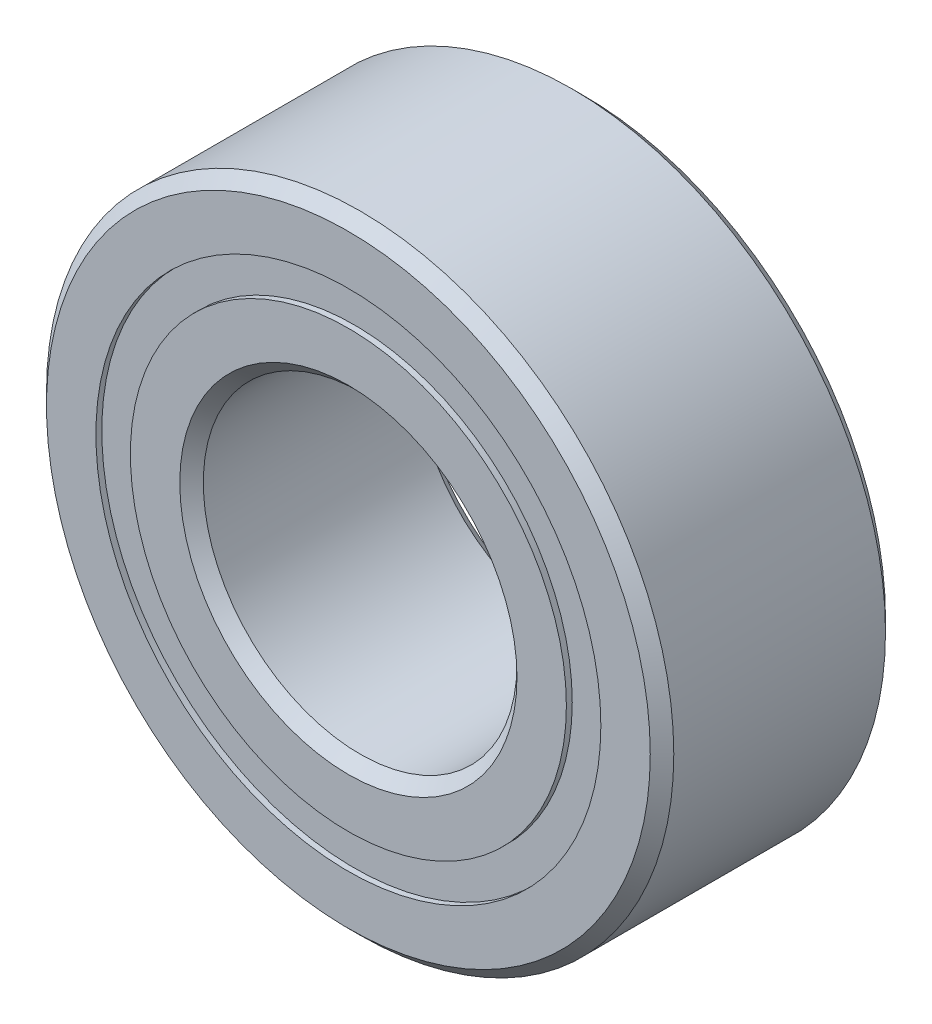
SolidWorks part; units mm, degrees
material "Ceramic Porcelain"
ref_plane "Front Plane" through (0, 0, 0) normal (0, 0, 1) x (1, 0, 0)
ref_plane "Top Plane" through (0, 0, 0) normal (0, 1, 0) x (1, 0, 0)
ref_plane "Right Plane" through (0, 0, 0) normal (1, 0, 0) x (0, 0, -1)
sketch "Sketch1" plane through (0, 0, 0) normal (1, 0, 0) x (0, 0, -1)
  line L0 (-3, 0) -> (3, 0) construction
  line L1 (0, 8) -> (0, -8) construction
  line L2 (2.7, 8) -> (-2.7, 8)
  line L3 (-2.7, 8) -> (-3, 7.7)
  line L4 (-3, 7.7) -> (-3, 6.4396)
  line L5 (-3, 6.4396) -> (-1.3333, 6.4396)
  line L6 (3, 6.4396) -> (1.3333, 6.4396)
  line L7 (3, 7.7) -> (3, 6.4396)
  line L8 (2.7, 8) -> (3, 7.7)
  line L9 (0, 8) -> (0, 6) construction
  line L10 (0, 6) -> (0, 4) construction
  arc A0 (-1.3333, 6.4396) -> (1.3333, 6.4396) centre (0, 6) cw
  point P14 (0, 4)
  dimension "D3" = 2.6667
  dimension "D1" = 45
  dimension "Width" = 6
  dimension "OD" = 16
  dimension "D2" = 0.3
  dimension "Shaft Dia" = 8
  dimension "D4" = 0.4396
revolve "Revolve1" add sketch "Sketch1" angle 360 about L0
sketch "Sketch3" plane through (0, 0, 0) normal (1, 0, 0) x (0, 0, -1)
  line L0 (-3, 5.5604) -> (-1.3333, 5.5604)
  line L1 (0, 8) -> (0, -8) construction
  line L2 (-3, 7.7) -> (-3, 6.4396) construction
  line L3 (-3, 5.5604) -> (-3, 4.3)
  line L4 (-2.7, 8) -> (-3, 7.7) construction
  line L5 (-3, 4.3) -> (-2.7, 4)
  line L6 (-2.7, 4) -> (2.7, 4)
  line L7 (2.7, 8) -> (2.7, -8) construction
  line L8 (2.7, 4) -> (3, 4.3)
  line L9 (3, -7.7) -> (3, 7.7) construction
  line L10 (3, 4.3) -> (3, 5.5604)
  line L11 (3, 5.5604) -> (1.3333, 5.5604)
  line L13 (2.7, 8) -> (3, 7.7) construction
  arc A0 (1.3333, 6.4396) -> (-1.3333, 6.4396) centre (0, 6) ccw construction
  arc A1 (1.3333, 5.5604) -> (-1.3333, 5.5604) centre (0, 6) cw
revolve "Revolve3" add sketch "Sketch3" angle 360 about L0
sketch "Sketch4" plane through (0, 0, 0) normal (1, 0, 0) x (0, 0, -1)
  line L0 (-1.4039, 6) -> (1.4039, 6)
  arc A2 (-1.4039, 6) -> (1.4039, 6) centre (0, 6) cw
  arc A3 (1.3333, 6.4396) -> (-1.3333, 6.4396) centre (0, 6) ccw construction
revolve "Revolve4" add sketch "Sketch4" angle 360 about L0
ref_axis "Axis1" through (0, 0, -3) along (0, 0, 1)
pattern_circular "CirPattern1" count 12 every 30 about axis through (0, 0, -3) along (0, 0, 1) of bodies 104
sketch "Sketch5" plane through (0, 0, 0) normal (1, 0, 0) x (0, 0, -1)
  line L0 (-3, 6.4396) -> (-1.3333, 6.4396) construction
  line L1 (-2.85, 6.4396) -> (-1.4039, 6.4396)
  line L2 (-2.85, 6.4396) -> (-2.85, 5.5604)
  line L3 (-2.85, 5.5604) -> (-1.4039, 5.5604)
  line L4 (-1.4039, 6.4396) -> (-1.4039, 5.5604)
  line L5 (-3, 5.5604) -> (-1.3333, 5.5604) construction
  line L6 (3, 6.4396) -> (1.3333, 6.4396) construction
  line L7 (2.85, 6.4396) -> (1.4039, 6.4396)
  line L8 (2.85, 6.4396) -> (2.85, 5.5604)
  line L9 (2.85, 5.5604) -> (1.4039, 5.5604)
  line L10 (1.4039, 6.4396) -> (1.4039, 5.5604)
  line L11 (3, 5.5604) -> (1.3333, 5.5604) construction
  line L12 (-2.7, 8) -> (-3, 7.7) construction
  point P18 (-2.85, 7.85)
revolve "Revolve5" add sketch "Sketch5" angle 360 about L0
sketch "Sketch6" plane through (0, 0, 0) normal (1, 0, 0) x (0, 0, -1)
  line L0 (3, 0) -> (-3, 0) construction
  line L1 (3, 6.4396) -> (2.2126, 6.4396)
  line L2 (3, 6.4396) -> (3, 6.9469)
  line L3 (3, 6.9469) -> (2.2126, 6.9469)
  line L4 (2.2126, 6.4396) -> (2.2126, 6.9469)
  dimension "Th" = 0.7874
  dimension "Flange OD" = 13.8938
revolve "Revolve6" [suppressed] add sketch "Sketch6" angle 360 about L0
equation "\"D2@Sketch1\" = \"Width@Sketch1\"*.05"
equation "\"D3@Sketch1\" = \"Width@Sketch1\"/2.25"
equation "\"D4@Sketch1\" = (((\"OD@Sketch1\"-\"Width@Sketch1\")/2)/3.25)/3.5"
equation "\"D2@CirPattern1\" = 360/\"Balls@CirPattern1\""
